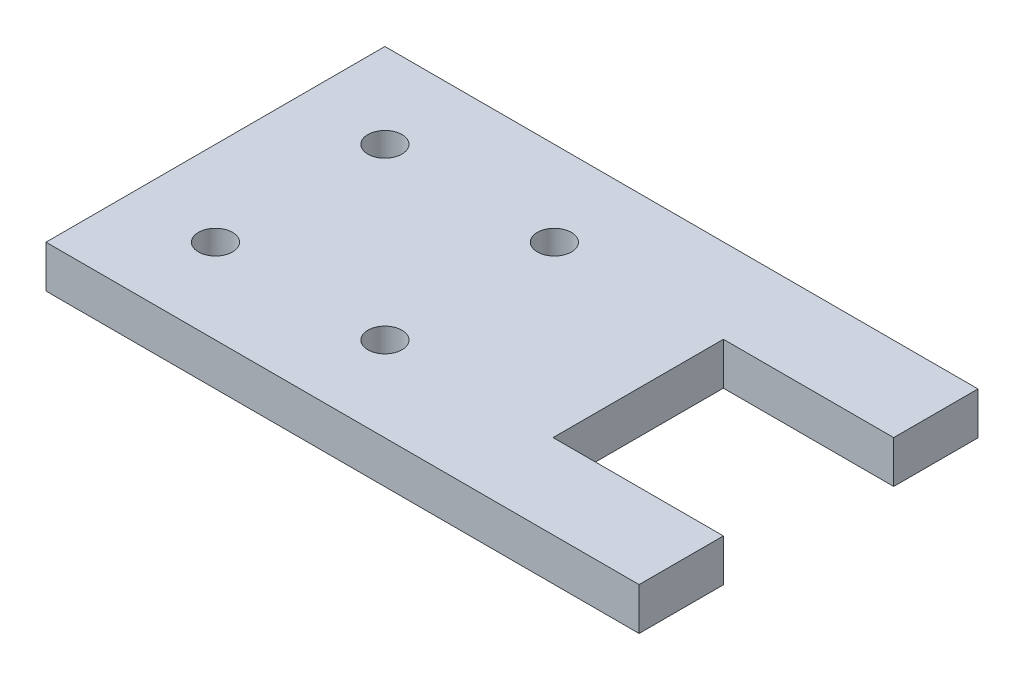
SolidWorks part; units mm, degrees
ref_plane "Front Plane" through (0, 0, 0) normal (0, 0, 1) x (1, 0, 0)
ref_plane "Top Plane" through (0, 0, 0) normal (0, 1, 0) x (1, 0, 0)
ref_plane "Right Plane" through (0, 0, 0) normal (1, 0, 0) x (0, 0, -1)
sketch "Sketch1" plane through (0, 0, 0) normal (0, 1, 0) x (1, 0, 0)
  line L0 (31.75, 25.4) -> (57.15, 25.4)
  line L1 (-31.75, -25.4) -> (31.75, -25.4)
  line L2 (-31.75, -25.4) -> (-31.75, 25.4)
  line L3 (-31.75, 25.4) -> (31.75, 25.4)
  line L5 (-31.75, -25.4) -> (31.75, 25.4) construction
  line L6 (-31.75, 25.4) -> (31.75, -25.4) construction
  line L7 (57.15, 25.4) -> (57.15, -25.4)
  line L8 (57.15, -25.4) -> (31.75, -25.4)
  point P0 (0, 0)
  dimension "D1" = 63.5
  dimension "D2" = 50.8
  dimension "D3" = 25.4
extrude "Boss-Extrude1" add sketch "Sketch1" along normal blind 6.35
sketch "Sketch2" plane through (0, 6.35, 0) normal (0, 1, 0) x (1, 0, 0)
  line L4 (57.15, 25.4) -> (-31.75, 25.4) construction
  line L5 (-31.75, -25.4) -> (57.15, -25.4) construction
  line L7 (19.05, 25.4) -> (19.05, -25.4) construction
  line L8 (-31.75, 25.4) -> (-31.75, -25.4) construction
  dimension "D1" = 50.8
hole_wizard "#10 Clearance Hole1" positions "Sketch3" profile "Sketch4" hole size "#10" standard "ANSI Inch" end condition through all
sketch "Sketch3" plane through (0, 6.35, 0) normal (0, 1, 0) x (1, 0, 0)
  line L4 (-19.05, 25.4) -> (-19.05, -25.4) construction
  line L5 (57.15, 25.4) -> (-31.75, 25.4) construction
  line L6 (-31.75, -25.4) -> (57.15, -25.4) construction
  line L8 (6.35, 25.4) -> (6.35, -25.4) construction
  line L9 (-31.75, 25.4) -> (-31.75, -25.4) construction
  line L11 (-31.75, 12.7) -> (19.05, 12.7) construction
  line L13 (-31.75, -12.7) -> (19.05, -12.7) construction
  point P0 (-19.05, 12.7)
  point P2 (6.35, 12.7)
  point P4 (6.35, -12.7)
  point P6 (-19.05, -12.7)
  dimension "D1" = 12.7
  dimension "D2" = 38.1
  dimension "D3" = 12.7
  dimension "D4" = 12.7
  dimension "D5" = 50.8
  dimension "D6" = 50.8
sketch "Sketch4" plane through (-19.05, 6.35, -12.7) normal (1, 0, 0) x (0, 0, 1)
  line L0 (0, 0) -> (0, 6.35)
  line L1 (0, 6.35) -> (2.5527, 6.35)
  line L2 (2.5527, 6.35) -> (2.5527, 0)
  line L5 (2.5527, 0) -> (0, 0)
  line L11 (0, -6.35) -> (0, 107.95) construction
  dimension "Thru Hole Dia." = 5.1054
  dimension "Thru Hole Depth" = 6.35
sketch "Sketch5" plane through (0, 6.35, 0) normal (0, 1, 0) x (1, 0, 0)
  line L1 (57.15, -25.4) -> (57.15, 25.4) construction
  line L2 (31.623, -12.7635) -> (57.15, -12.7635)
  line L4 (31.623, -12.7635) -> (31.623, 12.7635)
  line L5 (31.623, 12.7635) -> (57.15, 12.7635)
  line L6 (57.15, -12.7635) -> (57.15, 12.7635)
  line L7 (31.623, -12.7635) -> (57.15, 12.7635) construction
  line L8 (31.623, 12.7635) -> (57.15, -12.7635) construction
  line L13 (57.15, 12.7635) -> (57.15, 25.4) construction
  line L14 (57.15, -12.7635) -> (57.15, -25.4) construction
  dimension "D3" = 25.527
extrude "Cut-Extrude1" cut sketch "Sketch5" against normal through all
